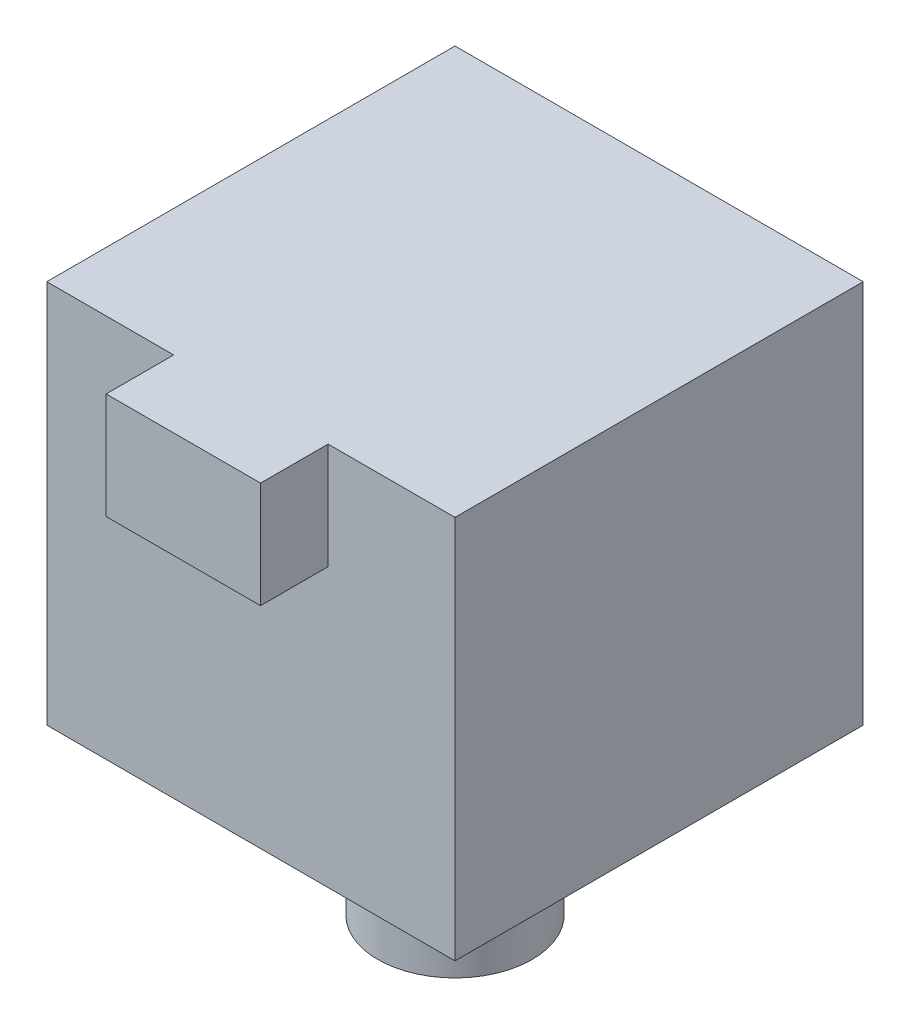
SolidWorks part; units mm, degrees
ref_plane "Front Plane" through (0, 0, 0) normal (0, 0, 1) x (1, 0, 0)
ref_plane "Top Plane" through (0, 0, 0) normal (0, 1, 0) x (1, 0, 0)
ref_plane "Right Plane" through (0, 0, 0) normal (1, 0, 0) x (0, 0, -1)
sketch "Sketch2" plane through (0, 0, 0) normal (0, 1, 0) x (1, 0, 0)
  line L1 (-21.15, -21.15) -> (21.15, -21.15)
  line L2 (-21.15, -21.15) -> (-21.15, 21.15)
  line L3 (-21.15, 21.15) -> (21.15, 21.15)
  line L4 (21.15, -21.15) -> (21.15, 21.15)
  line L5 (-21.15, -21.15) -> (21.15, 21.15) construction
  line L6 (-21.15, 21.15) -> (21.15, -21.15) construction
  point P0 (0, 0)
  dimension "D1" = 42.3
extrude "Boss-Extrude2" add sketch "Sketch2" along normal blind 39.8
sketch "Sketch4" plane through (0, 0, 0) normal (0, -1, 0) x (1, 0, 0)
  circle A0 centre (0, 0) radius 11
  dimension "D1" = 22
extrude "Boss-Extrude3" add sketch "Sketch4" along normal blind 2.032
sketch "Sketch6" plane through (0, 0, 0) normal (0, -1, 0) x (1, 0, 0)
  line L1 (-15.5, -15.5) -> (15.5, -15.5) construction
  line L2 (-15.5, -15.5) -> (-15.5, 15.5) construction
  line L3 (-15.5, 15.5) -> (15.5, 15.5) construction
  line L4 (15.5, -15.5) -> (15.5, 15.5) construction
  line L5 (-15.5, -15.5) -> (15.5, 15.5) construction
  line L6 (-15.5, 15.5) -> (15.5, -15.5) construction
  circle A0 centre (15.5, 15.5) radius 1.5
  circle A1 centre (-15.5, 15.5) radius 1.5
  circle A2 centre (-15.5, -15.5) radius 1.5
  circle A3 centre (15.5, -15.5) radius 1.5
  point P0 (0, 0)
  dimension "D2" = 3
  dimension "D1" = 31
extrude "Cut-Extrude1" cut sketch "Sketch6" against normal blind 2
sketch "Sketch7" plane through (0, 0, 21.15) normal (0, 0, 1) x (1, 0, 0)
  line L0 (-21.15, 39.8) -> (21.15, 39.8) construction
  line L1 (-8, 39.8) -> (8, 39.8)
  line L2 (-8, 39.8) -> (-8, 28.8)
  line L3 (-8, 28.8) -> (8, 28.8)
  line L4 (8, 39.8) -> (8, 28.8)
  line L5 (-8, 39.8) -> (8, 28.8) construction
  line L6 (-8, 28.8) -> (8, 39.8) construction
  line L7 (-21.15, 39.8) -> (21.15, 39.8) construction
  line L8 (0, 0) -> (0, 39.8) construction
  point P0 (0, 34.3)
  dimension "D1" = 16
  dimension "D2" = 11
extrude "Boss-Extrude4" add sketch "Sketch7" along normal blind 7
sketch "Sketch9" plane through (0, -2.032, 0) normal (0, -1, 0) x (1, 0, 0)
  circle A0 centre (0, 0) radius 2.5
  dimension "D1" = 5
extrude "Boss-Extrude5" add sketch "Sketch9" along normal blind 15
ref_axis "Main_Axis" through (0, -17.032, 0) along (0, 1, 0)
ref_point "Arm_Refernce_Point"
ref_axis "Arm_Alignment_Axis" through (0, 19.9, -21.15) along (0, 0, 1)
sketch "Sketch11" plane through (0, -17.032, 0) normal (0, -1, 0) x (1, 0, 0)
  circle A0 centre (0, 0) radius 8
  circle A1 centre (0, 0) radius 2.5 construction
  circle A2 centre (0, 0) radius 2.5
  dimension "D1" = 16
extrude "Boss-Extrude7" add sketch "Sketch11" against normal blind 11
sketch "Sketch13" plane through (0, -17.032, 0) normal (0, -1, 0) x (1, 0, 0)
  circle A1 centre (0, 0) radius 2.5
  circle A2 centre (0, 0) radius 2.5
  dimension "D1" = 0
extrude "Boss-Extrude8" add sketch "Sketch13" along normal blind 0.8
ref_axis "Screw_Axis_1" through (15.5, 2, -15.5) along (0, -1, 0)
ref_axis "Screw_Axis_2" through (-15.5, 2, -15.5) along (0, -1, 0)
ref_axis "Screw_Axis_3" through (15.5, 2, 15.5) along (0, -1, 0)
ref_axis "Screw_Axis_4" through (-15.5, 2, 15.5) along (0, -1, 0)
